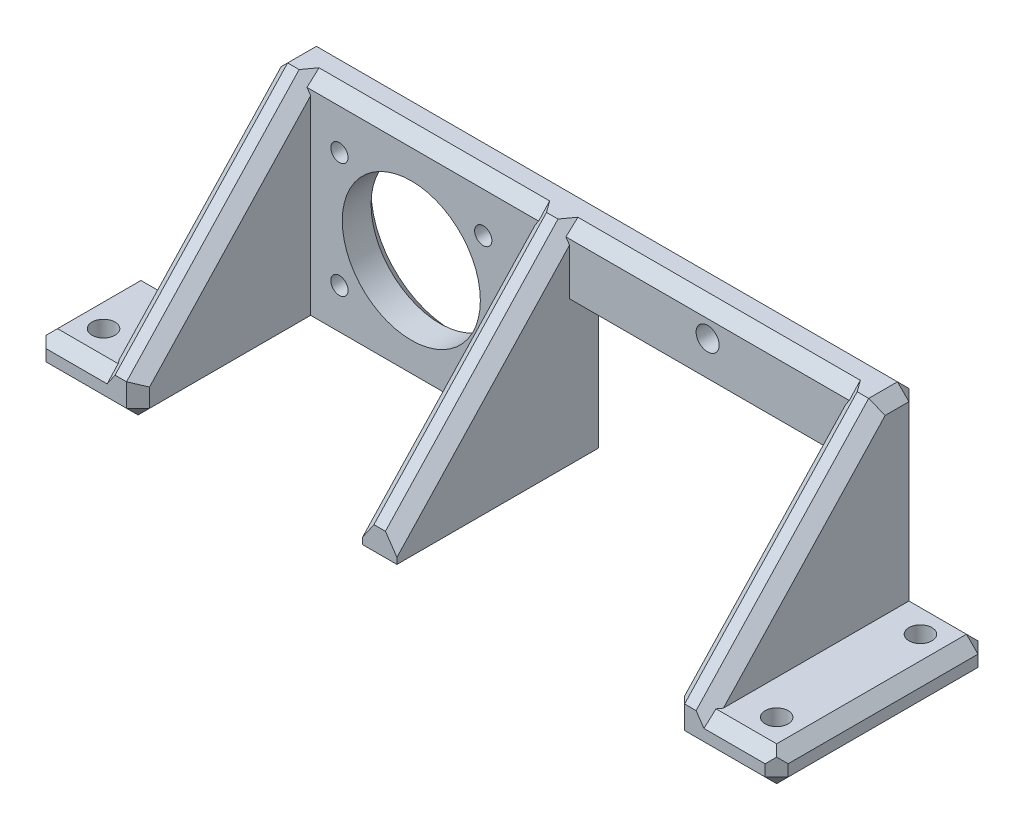
SolidWorks part; units mm, degrees
note: The reader was unsure of these and kept them because the rebuilt part matched: shared geometry of "Sketch2<3>", "Sketch2<4>".
ref_plane "Front Plane" through (0, 0, 0) normal (0, 0, 1) x (1, 0, 0)
ref_plane "Top Plane" through (0, 0, 0) normal (0, 1, 0) x (1, 0, 0)
ref_plane "Right Plane" through (0, 0, 0) normal (1, 0, 0) x (0, 0, -1)
sketch "Sketch1" plane through (0, 0, 0) normal (0, 0, 1) x (1, 0, 0)
  line L1 (0, 0) -> (45, 0)
  line L2 (0, 0) -> (0, 38)
  line L3 (0, 38) -> (99, 38)
  line L4 (45, 0) -> (45, 27)
  line L7 (45, 27) -> (93, 27)
  line L10 (93, 27) -> (93, 0)
  line L11 (93, 0) -> (99, 0)
  line L12 (99, 38) -> (99, 0)
  circle A0 centre (17.5, 19) radius 12
  circle A1 centre (5, 29) radius 1.5
  circle A2 centre (5, 9) radius 1.5
  circle A3 centre (30, 9) radius 1.5
  circle A4 centre (30, 29) radius 1.5
  circle A5 centre (69, 33) radius 2
  point P16 (69, 27)
  point P18 (0, 19)
  dimension "D3" = 24
  dimension "D9" = 3
  dimension "D14" = 4
  dimension "D1" = 38
  dimension "D2" = 45
  dimension "D4" = 48
  dimension "D5" = 20
  dimension "D6" = 25
  dimension "D7" = 12.5
  dimension "D8" = 10
  dimension "D10" = 5
  dimension "D11" = 27
  dimension "D12" = 6
  dimension "D13" = 6
extrude "Boss-Extrude1" add sketch "Sketch1" along normal blind 7
sketch "Sketch2" plane through (99, 0, 0) normal (1, 0, 0) x (0, 0, -1)
  line L1 (-37, 0) -> (-7, 0)
  line L3 (-37, 0) -> (-37, 6)
  line L4 (0, 0) -> (-7, 0)
  line L5 (0, 0) -> (0, 38)
  line L6 (0, 38) -> (-7, 38)
  line L8 (-37, 6) -> (-7, 38)
  dimension "D1" = 30
  dimension "D2" = 6
extrude "Boss-Extrude2" add sketch "Sketch2" against normal blind 6
extrude "Boss-Extrude3" add sketch "Sketch2<3>" against normal blind 6 from surface at -99 starting at face at (0, 19, 3.5)
sketch "Sketch2<3>" plane through (99, 0, 0) normal (1, 0, 0) x (0, 0, -1) same geometry as "Sketch2"
extrude "Boss-Extrude4" add sketch "Sketch2<4>" against normal blind 6 from surface at -54 starting at face at (45, 13.5, 3.5)
sketch "Sketch2<4>" plane through (99, 0, 0) normal (1, 0, 0) x (0, 0, -1) same geometry as "Sketch2"
sketch "Sketch3" plane through (0, 0, 0) normal (0, -1, 0) x (-1, 0, 0)
  line L1 (6, 0) -> (18, 0)
  line L2 (6, 0) -> (6, -37)
  line L3 (6, -37) -> (18, -37)
  line L4 (18, 0) -> (18, -37)
  line L5 (-46.5, 0) -> (-46.5, -44.3915) construction
  line L6 (6, 0) -> (-45, 0) construction
  line L7 (-99, -37) -> (-99, 0) construction
  line L8 (-99, -37) -> (-111, -37)
  line L9 (-111, 0) -> (-111, -37)
  line L10 (-99, 0) -> (-111, 0)
  line L11 (-99, 0) -> (-99, -37)
  line L12 (6, -37) -> (0, -37) construction
  circle A0 centre (12, -31) radius 2
  circle A1 centre (12, -6) radius 2
  circle A2 centre (-105, -31) radius 2
  circle A3 centre (-105, -6) radius 2
  point P11 (12, -37)
  dimension "D2" = 4
  dimension "D1" = 25
  dimension "D3" = 12
  dimension "D4" = 6
  dimension "D5" = 52.5
extrude "Boss-Extrude5" add sketch "Sketch3" against normal blind 6
sketch "Sketch4" plane through (0, 6, 0) normal (0, 1, 0) x (1, 0, 0)
  line L0 (-6, 0) -> (-6, -37) construction
  line L1 (-18, 0) -> (-6, 0)
  line L2 (-18, 0) -> (-18, -18.5)
  line L3 (-18, -18.5) -> (-6, -18.5)
  line L4 (-6, 0) -> (-6, -18.5)
extrude "Cut-Extrude1" cut sketch "Sketch4" against normal blind 10
chamfer "Chamfer1" distance 2 angle 45 36 edges at (29.5, 19, 0) (69, 38, 7) (19.5, 38, 7) (111, 0, 18.5) (111, 6, 18.5) (19.5, 0, 7) (0, 0, 22) (93, 0, 18.5) (93, 3, 37) (102, 0, 37) (0, 3, 37) (39, 0, 22) (42, 0, 37) (45, 0, 18.5) (-9, 0, 37) (-18, 3, 37) (-18, 0, 27.75) (-18, 6, 27.75) (19.5, 0, 0) (45, 13.5, 0) (69, 27, 0) (93, 13.5, 0) (102, 0, 0) (111, 3, 37) (111, 3, 0) (105, 6, 0) (99, 22, 22) (99, 38, 3.5) (-6, 22, 22) (-6, 38, 3.5) (-6, 19, 0) (99, 22, 0) (46.5, 38, 0) (-12, 0, 18.5) (-12, 6, 18.5) (-6, 0, 9.25)
chamfer "Chamfer2" distance 2 angle 45 6 edges at (103, 6, 37) (-10, 6, 37) (0, 23.0667, 21) (93, 23.0667, 21) (39, 22, 22) (45, 22, 22)
